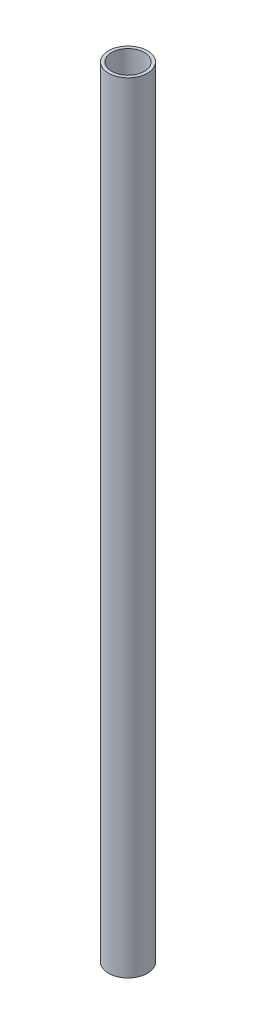
SolidWorks part; units mm, degrees
ref_plane "Front Plane" through (0, 0, 0) normal (0, 0, 1) x (1, 0, 0)
ref_plane "Top Plane" through (0, 0, 0) normal (0, 1, 0) x (1, 0, 0)
ref_plane "Right Plane" through (0, 0, 0) normal (1, 0, 0) x (0, 0, -1)
sketch "Sketch1" plane through (0, 0, 0) normal (0, 1, 0) x (1, 0, 0)
  circle A0 centre (0, 0) radius 12.5
  circle A1 centre (0, 0) radius 10.5
  dimension "D1" = 25
  dimension "D2" = 21
extrude "Boss-Extrude1" add sketch "Sketch1" along normal blind 500
equation "\"D1@Sketch1\" = \"cf_tube_outer_diameter\""
equation "\"D1@Boss-Extrude1\"= \"mid_tube_length\""
equation "\"cf_tube_outer_diameter\" = 25mm"
equation "\"mid_plate_mid_to_top\" = 100mm"
equation "\"mid_plate_mid_to_bottom\" = 125mm"
equation "\"mid_plate_horizontal_spacing\" = 250mm"
equation "\"mid_tube_length\" = 500mm"
equation "\"cf_tube_inner_diameter\" = 21mm"
equation "\"D2@Sketch1\"=\"cf_tube_inner_diameter\""
